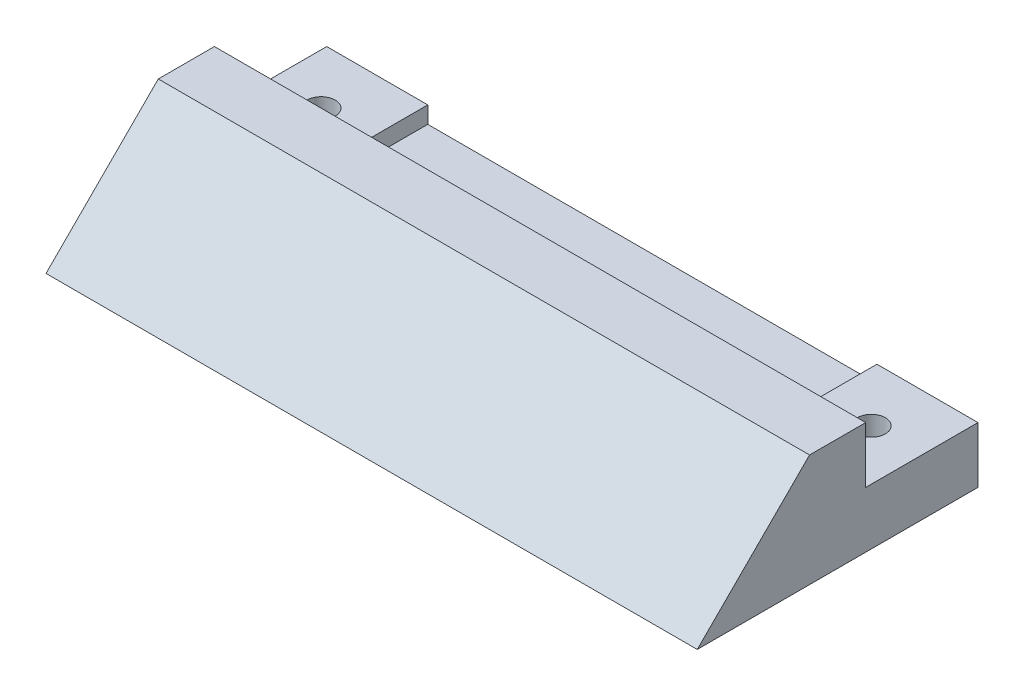
SolidWorks part; units mm, degrees
ref_plane "Front Plane" through (0, 0, 0) normal (0, 0, 1) x (1, 0, 0)
ref_plane "Top Plane" through (0, 0, 0) normal (0, 1, 0) x (1, 0, 0)
ref_plane "Right Plane" through (0, 0, 0) normal (1, 0, 0) x (0, 0, -1)
sketch "Sketch1" plane through (0, 0, 0) normal (1, 0, 0) x (0, 0, -1)
  line L0 (0, 0) -> (0, 10)
  line L1 (0, 10) -> (-15, 10)
  line L2 (-15, 10) -> (-25, 0)
  line L3 (-25, 0) -> (0, 0)
  dimension "D1" = 45
  dimension "D2" = 15
  dimension "D3" = 10
extrude "Boss-Extrude1" add sketch "Sketch1" along normal blind 58
sketch "Sketch2" plane through (0, 10, 0) normal (0, 1, 0) x (1, 0, 0)
  line L0 (58, 0) -> (0, 0) construction
  line L1 (9, 0) -> (49, 0)
  line L2 (9, 0) -> (9, -10)
  line L3 (9, -10) -> (49, -10)
  line L4 (49, 0) -> (49, -10)
  line L5 (0, 0) -> (0, -15) construction
  dimension "D1" = 10
  dimension "D2" = 40
  dimension "D3" = 9
extrude "Cut-Extrude1" cut sketch "Sketch2" against normal blind 6.5
sketch "Sketch3" plane through (0, 10, 0) normal (0, 1, 0) x (1, 0, 0)
  line L0 (58, 0) -> (58, -15) construction
  line L1 (0, 0) -> (58, 0)
  line L2 (0, 0) -> (0, -10)
  line L3 (0, -10) -> (58, -10)
  line L4 (58, 0) -> (58, -10)
  line L5 (9, -10) -> (49, -10) construction
extrude "Cut-Extrude2" cut sketch "Sketch3" against normal offset from surface (5 mm away) 1.5 up to face at (29, 3.5, 5)
sketch "Sketch4" plane through (0, 5, 0) normal (0, 1, 0) x (1, 0, 0)
  line L0 (0, -10) -> (0, 0) construction
  line L1 (9, -10) -> (0, -10) construction
  line L2 (9, 0) -> (9, -10) construction
  line L3 (49, 0) -> (49, -10) construction
  line L5 (58, 0) -> (58, -10) construction
  circle A0 centre (4.5, -5) radius 1.25
  circle A1 centre (14, -5) radius 1.25
  circle A2 centre (29, -5) radius 1.25
  circle A3 centre (44, -5) radius 1.25
  circle A4 centre (53.5, -5) radius 1.25
  dimension "D1" = 2.5
  dimension "D2" = 4.5
  dimension "D3" = 5
  dimension "D4" = 5
  dimension "D5" = 5
  dimension "D6" = 20
  dimension "D7" = 4.5
extrude "Cut-Extrude3" cut sketch "Sketch4" against normal up to next
fillet "Fillet1" radius 3 2 edges at (9, 4.25, 10) (49, 4.25, 10)
